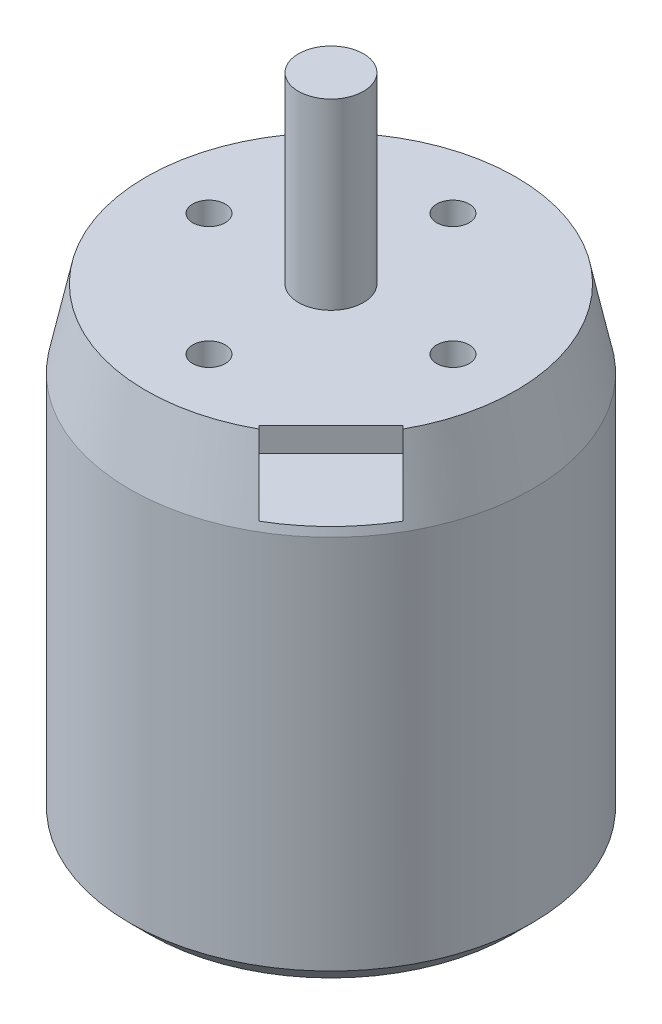
SolidWorks part; units mm, degrees
material "Plain Carbon Steel"
ref_plane "Front Plane" through (0, 0, 0) normal (0, 0, 1) x (1, 0, 0)
ref_plane "Top Plane" through (0, 0, 0) normal (0, 1, 0) x (1, 0, 0)
ref_plane "Right Plane" through (0, 0, 0) normal (1, 0, 0) x (0, 0, -1)
sketch "Sketch1" plane through (0, 0, 0) normal (0, 1, 0) x (1, 0, 0)
  circle A0 centre (0, 0) radius 24.75
  dimension "D1" = 49.5
extrude "Boss-Extrude1" add sketch "Sketch1" along normal blind 58.2
sketch "Sketch2" plane through (0, 58.2, 0) normal (0, 1, 0) x (1, 0, 0)
  circle A0 centre (0, 0) radius 4
  dimension "D1" = 8
extrude "Boss-Extrude2" add sketch "Sketch2" along normal blind 22.5
chamfer "Chamfer1" distance 2.5 angle 45 1 edges at (0, 0, 24.75)
sketch "Sketch3" plane through (0, 0, 0) normal (0, -1, 0) x (1, 0, 0)
  circle A0 centre (0, 0) radius 6.8
  dimension "D1" = 13.6
extrude "Boss-Extrude3" add sketch "Sketch3" along normal blind 2
fillet "Fillet1" radius 0.5 1 edges at (0, 0, -6.8)
sketch "Sketch4" plane through (0, 58.2, 0) normal (0, 1, 0) x (1, 0, 0)
  circle A0 centre (0, 0) radius 15 construction
  circle A1 centre (0, 15) radius 2
  circle A2 centre (15, 0) radius 2
  circle A3 centre (0, -15) radius 2
  circle A4 centre (-15, 0) radius 2
  point P3 (0, 15)
  point P4 (-15, 0)
  point P5 (0, -15)
  point P6 (15, 0)
  dimension "D1" = 30
  dimension "D2" = 4
extrude "Cut-Extrude1" cut sketch "Sketch4" against normal blind 10
sketch "Sketch5" plane through (0, 0, 0) normal (0, -1, 0) x (1, 0, 0)
  circle A0 centre (0, 0) radius 9.875 construction
  circle A1 centre (0, 9.875) radius 1.5
  circle A2 centre (9.875, 0) radius 1.5
  circle A3 centre (0, -9.875) radius 1.5
  circle A4 centre (-9.875, 0) radius 1.5
  dimension "D1" = 19.75
  dimension "D2" = 3
extrude "Cut-Extrude2" cut sketch "Sketch5" against normal blind 5
chamfer "Chamfer2" distance 9.5 distance2 2 1 edges at (0, 58.2, 24.75) first distance on face at (0, 2.5, 24.75)
sketch "Sketch6" plane through (0, 58.2, 0) normal (0, 1, 0) x (1, 0, 0)
  line L0 (0, -22.75) -> (0, 0) construction
  line L1 (0, 0) -> (22.75, 0) construction
  line L2 (22.75, 0) -> (0, -22.75) construction
  line L3 (0, 0) -> (16.0867, -16.0867) construction
  line L4 (19.5161, -10.6773) -> (10.6773, -19.5161)
  line L5 (19.5161, -10.6773) -> (26.5872, -17.7484)
  line L6 (10.6773, -19.5161) -> (17.7484, -26.5872)
  line L7 (26.5872, -17.7484) -> (17.7484, -26.5872)
  circle A0 centre (0, 0) radius 22.75 construction
  dimension "D1" = 1.4
  dimension "D2" = 12.5
  dimension "D3" = 10
extrude "Cut-Extrude3" cut sketch "Sketch6" against normal blind 8.5
sketch "Sketch7" plane through (15.0967, 0, 15.0967) normal (0.7071, 0, 0.7071) x (0.7071, 0, -0.7071)
  line L0 (6.25, 49.7) -> (6.25, 58.2) construction
  line L1 (-6.25, 49.7) -> (6.25, 49.7)
  line L2 (-6.25, 49.7) -> (-6.25, 55.2)
  line L3 (-6.25, 55.2) -> (6.25, 55.2)
  line L4 (6.25, 49.7) -> (6.25, 55.2)
  line L5 (-6.25, 49.7) -> (6.25, 55.2) construction
  line L6 (-6.25, 55.2) -> (6.25, 49.7) construction
  line L7 (6.25, 58.2) -> (-6.25, 58.2) construction
  point P4 (0, 52.45)
  dimension "D1" = 3
extrude "Cut-Extrude4" cut sketch "Sketch7" against normal blind 8.5
ref_axis "Axis1" through (0, 48.7, 0) along (0, -1, 0)
